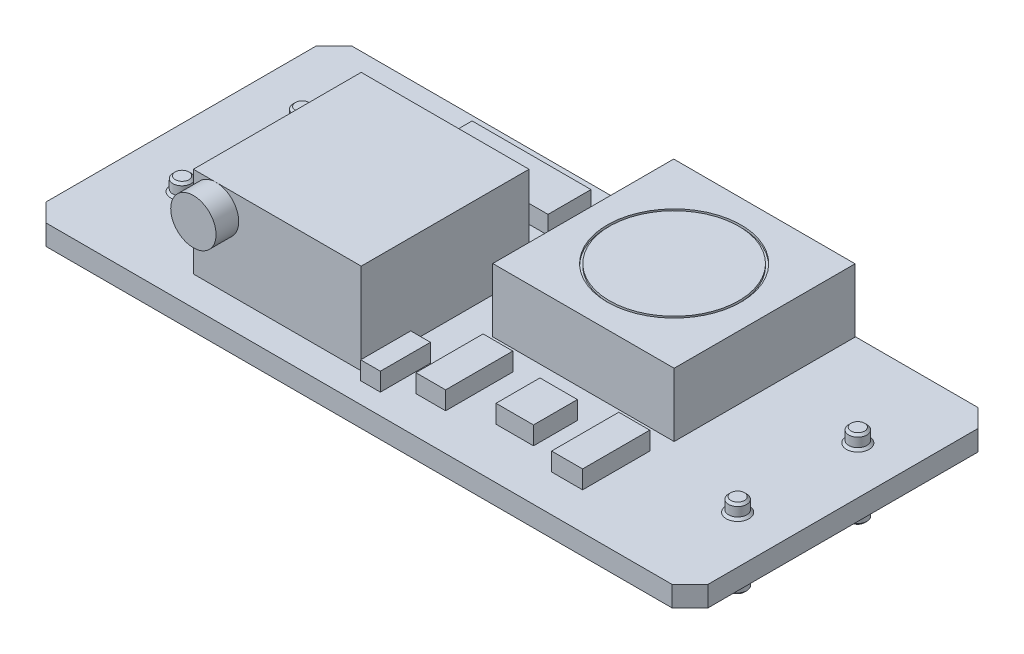
SolidWorks part; units mm, degrees
ref_plane "Front Plane" through (0, 0, 0) normal (0, 0, 1) x (1, 0, 0)
ref_plane "Top Plane" through (0, 0, 0) normal (0, 1, 0) x (1, 0, 0)
ref_plane "Right Plane" through (0, 0, 0) normal (1, 0, 0) x (0, 0, -1)
sketch "Sketch1" plane through (0, 0, 0) normal (0, 1, 0) x (1, 0, 0)
  line L1 (0, 0) -> (37.084, 0)
  line L2 (0, 0) -> (0, 17.145)
  line L3 (0, 17.145) -> (37.084, 17.145)
  line L4 (37.084, 0) -> (37.084, 17.145)
  line L5 (18.542, 17.145) -> (18.542, 0) construction
  line L6 (0, 8.5725) -> (37.084, 8.5725) construction
  point P200 (18.542, 8.5725)
  dimension "D1" = 17.145
  dimension "D2" = 37.084
extrude "Boss-Extrude1" add sketch "Sketch1" along normal blind 1.143
sketch "Sketch2" plane through (0, 1.143, 0) normal (0, 1, 0) x (1, 0, 0)
  line L0 (3.302, 12.065) -> (3.302, 5.334)
  line L1 (0, 17.145) -> (3.302, 17.145)
  line L2 (0, 17.145) -> (0, 12.065)
  line L3 (0, 12.065) -> (3.302, 12.065)
  line L4 (3.302, 17.145) -> (3.302, 12.065)
  line L5 (1.651, 12.065) -> (1.651, 17.145) construction
  line L6 (0, 14.605) -> (3.302, 14.605) construction
  line L7 (3.302, 12.065) -> (34.417, 12.065)
  line L8 (3.302, 5.334) -> (34.417, 5.334)
  circle A0 centre (3.302, 12.065) radius 0.508
  circle A1 centre (3.302, 5.334) radius 0.508
  circle A2 centre (34.417, 12.065) radius 0.508
  circle A3 centre (34.417, 5.334) radius 0.508
  point P52 (1.651, 14.605)
  dimension "D3" = 1.016
  dimension "D5" = 1.016
  dimension "D7" = 1.016
  dimension "D9" = 1.016
  dimension "D1" = 5.08
  dimension "D2" = 3.302
  dimension "D4" = 6.731
  dimension "D6" = 31.115
  dimension "D8" = 31.115
extrude "Boss-Extrude2" add sketch "Sketch2" against normal blind 3.683 and the other way blind 0.762 contours A0 | A1 | A2 | A3
chamfer "Chamfer1" distance 0.127 angle 45 16 edges at (34.417, -2.54, -4.826) (34.417, 0, -5.842) (34.417, -2.54, -11.557) (34.417, 0, -12.573) (3.302, -2.54, -11.557) (3.302, 0, -12.573) (3.302, -2.54, -4.826) (3.302, 0, -5.842) (34.417, 1.143, -5.842) (34.417, 1.905, -4.826) (34.417, 1.143, -12.573) (34.417, 1.905, -11.557) (3.302, 1.143, -5.842) (3.302, 1.905, -4.826) (3.302, 1.143, -12.573) (3.302, 1.905, -11.557)
sketch "Sketch3" plane through (0, 1.143, 0) normal (0, 1, 0) x (1, 0, 0)
  line L0 (17.018, 11.049) -> (19.05, 11.049)
  line L1 (0, 17.145) -> (7.62, 17.145)
  line L2 (0, 17.145) -> (0, 11.049)
  line L3 (0, 11.049) -> (7.62, 11.049)
  line L4 (7.62, 17.145) -> (7.62, 11.049)
  line L5 (3.81, 11.049) -> (3.81, 17.145) construction
  line L6 (0, 14.097) -> (7.62, 14.097) construction
  line L7 (7.62, 11.049) -> (17.018, 11.049)
  line L8 (7.62, 11.049) -> (7.62, 1.651)
  line L9 (7.62, 1.651) -> (17.018, 1.651)
  line L10 (17.018, 11.049) -> (17.018, 1.651)
  line L11 (12.319, 1.651) -> (12.319, 11.049) construction
  line L12 (7.62, 6.35) -> (17.018, 6.35) construction
  line L13 (37.084, 17.145) -> (0, 17.145) construction
  line L14 (19.05, 17.145) -> (29.21, 17.145)
  line L15 (19.05, 17.145) -> (19.05, 6.985)
  line L16 (19.05, 6.985) -> (29.21, 6.985)
  line L17 (29.21, 17.145) -> (29.21, 6.985)
  line L18 (24.13, 6.985) -> (24.13, 17.145) construction
  line L19 (19.05, 12.065) -> (29.21, 12.065) construction
  point P92 (3.81, 14.097)
  point P193 (12.319, 6.35)
  point P295 (24.13, 12.065)
  line M8 (37.084, 17.145) -> (0, 17.145)
  dimension "D1" = 6.096
  dimension "D2" = 7.62
  dimension "D3" = 9.398
  dimension "D4" = 2.032
  dimension "D5" = 10.16
extrude "Boss-Extrude3" add sketch "Sketch3" along normal blind 5.08 contours L10 L7 L8 L9 region at (12.319, 1.143, -6.35)
extrude "Boss-Extrude4" add sketch "Sketch3<3>" along normal blind 3.556 contours L17 L15 L16 M8 region at (24.13, 1.143, -12.065)
sketch "Sketch3<3>" plane through (0, 1.143, 0) normal (0, 1, 0) x (1, 0, 0) same geometry as "Sketch3"
sketch "Sketch4" plane through (0, 0, -1.651) normal (0, 0, 1) x (1, 0, 0)
  line L1 (7.62, 6.223) -> (8.89, 6.223)
  line L2 (7.62, 6.223) -> (7.62, 4.953)
  line L3 (7.62, 4.953) -> (8.89, 4.953)
  line L4 (8.89, 6.223) -> (8.89, 4.953)
  line L5 (8.255, 4.953) -> (8.255, 6.223) construction
  line L6 (7.62, 5.588) -> (8.89, 5.588) construction
  circle A0 centre (8.89, 4.953) radius 1.27
  point P96 (8.255, 5.588)
  dimension "D2" = 2.54
  dimension "D1" = 1.27
extrude "Boss-Extrude5" add sketch "Sketch4" along normal blind 1.27 contours L3 A0 L4 | L4 A0 L3 region at (9.0697, 4.7733, -1.651) region at (8.351, 5.492, -1.651)
sketch "Sketch5" plane through (0, 4.699, 0) normal (0, 1, 0) x (1, 0, 0)
  line L1 (19.05, 17.145) -> (29.21, 17.145)
  line L2 (19.05, 17.145) -> (19.05, 6.985)
  line L3 (19.05, 6.985) -> (29.21, 6.985)
  line L4 (29.21, 17.145) -> (29.21, 6.985)
  line L5 (24.13, 6.985) -> (24.13, 17.145) construction
  line L6 (19.05, 12.065) -> (29.21, 12.065) construction
  circle A0 centre (24.13, 12.065) radius 3.6195
  circle A1 centre (24.13, 12.065) radius 3.7465
  point P148 (24.13, 12.065)
  dimension "D1" = 7.239
  dimension "D2" = 7.493
extrude "Cut-Extrude1" cut sketch "Sketch5" against normal blind 0.127 contours A1 | A0
sketch "Sketch6" plane through (0, 1.143, 0) normal (0, 1, 0) x (1, 0, 0)
  line L1 (9.017, 15.8632) -> (15.6746, 15.8632)
  line L2 (9.017, 15.8632) -> (9.017, 13.4571)
  line L3 (9.017, 13.4571) -> (15.6746, 13.4571)
  line L4 (15.6746, 15.8632) -> (15.6746, 13.4571)
  line L5 (12.3458, 13.4571) -> (12.3458, 15.8632) construction
  line L6 (9.017, 14.6602) -> (15.6746, 14.6602) construction
  line L7 (19.6546, 5.8407) -> (21.319, 5.8407)
  line L8 (19.6546, 5.8407) -> (19.6546, 2.0778)
  line L9 (19.6546, 2.0778) -> (21.319, 2.0778)
  line L10 (21.319, 5.8407) -> (21.319, 2.0778)
  line L11 (20.4868, 2.0778) -> (20.4868, 5.8407) construction
  line L12 (19.6546, 3.9593) -> (21.319, 3.9593) construction
  line L13 (27.2529, 5.8407) -> (28.9896, 5.8407)
  line L14 (27.2529, 5.8407) -> (27.2529, 2.0778)
  line L15 (27.2529, 2.0778) -> (28.9896, 2.0778)
  line L16 (28.9896, 5.8407) -> (28.9896, 2.0778)
  line L17 (28.1213, 2.0778) -> (28.1213, 5.8407) construction
  line L18 (27.2529, 3.9593) -> (28.9896, 3.9593) construction
  line L19 (23.3814, 5.298) -> (25.48, 5.298)
  line L20 (23.3814, 5.298) -> (23.3814, 2.8376)
  line L21 (23.3814, 2.8376) -> (25.48, 2.8376)
  line L22 (25.48, 5.298) -> (25.48, 2.8376)
  line L23 (24.4307, 2.8376) -> (24.4307, 5.298) construction
  line L24 (23.3814, 4.0678) -> (25.48, 4.0678) construction
  line L25 (17.4837, 3.9593) -> (18.5872, 3.9593)
  line L26 (17.4837, 3.9593) -> (17.4837, 1.1551)
  line L27 (17.4837, 1.1551) -> (18.5872, 1.1551)
  line L28 (18.5872, 3.9593) -> (18.5872, 1.1551)
  line L29 (18.0354, 1.1551) -> (18.0354, 3.9593) construction
  line L30 (17.4837, 2.5572) -> (18.5872, 2.5572) construction
  point P82 (20.4868, 3.9593)
  point P101 (24.4307, 4.0678)
  point P112 (12.3458, 14.6602)
  point P165 (18.0354, 2.5572)
  point P198 (28.1213, 3.9593)
extrude "Boss-Extrude6" add sketch "Sketch6" along normal blind 1.016
chamfer "Chamfer2" distance 1.016 angle 45 4 edges at (37.084, 0.5715, 0) (37.084, 0.5715, -17.145) (0, 0.5715, -17.145) (0, 0.5715, 0)
sketch "Sketch7" plane through (0, 0, -17.145) normal (0, 0, -1) x (-1, 0, 0)
  line L0 (-29.21, 1.143) -> (-19.05, 1.143)
  line L3 (-29.21, 1.143) -> (-29.21, 4.699)
  line L4 (-29.21, 4.699) -> (-19.05, 4.699)
  line L5 (-19.05, 1.143) -> (-19.05, 4.699)
  line L6 (-24.13, 4.699) -> (-24.13, 1.143) construction
  line L7 (-29.21, 2.921) -> (-19.05, 2.921) construction
  point P159 (-24.13, 2.921)
extrude "Cut-Extrude2" cut sketch "Sketch7" against normal blind 0.0254
